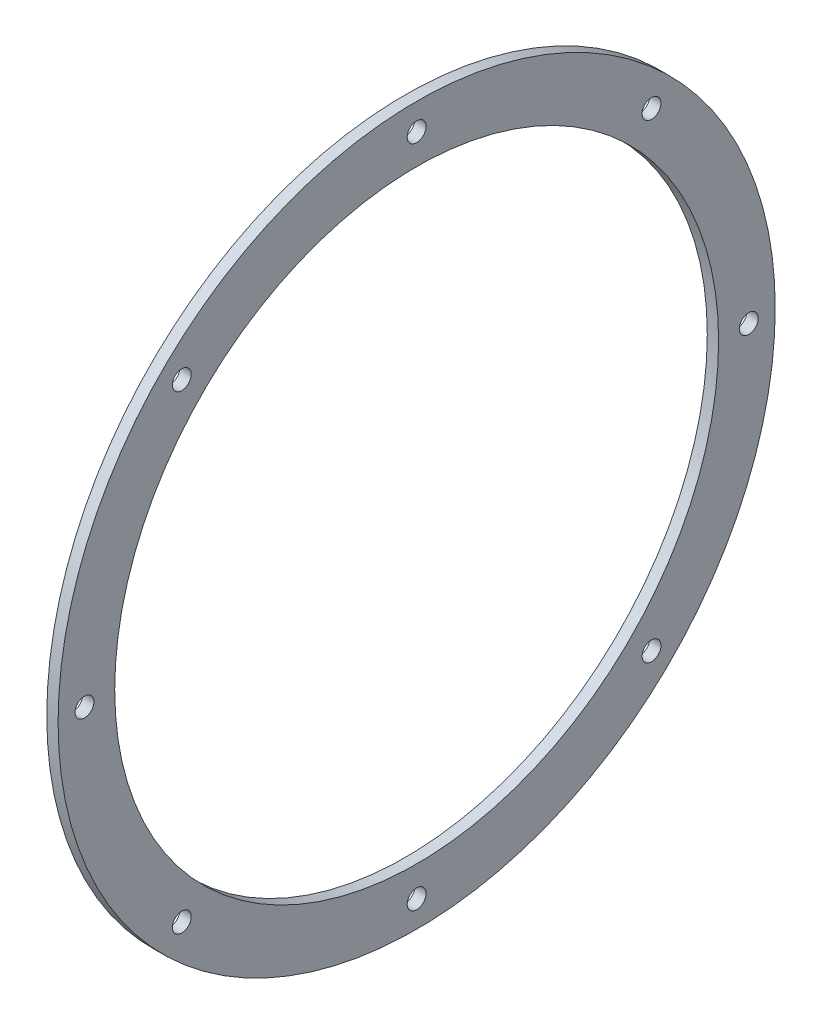
SolidWorks part; units mm, degrees
material "201 Stal nierdzewna odprężona (SS)"
ref_plane "Płaszczyzna przednia" through (0, 0, 0) normal (0, 0, 1) x (1, 0, 0)
ref_plane "Płaszczyzna górna" through (0, 0, 0) normal (0, 1, 0) x (1, 0, 0)
ref_plane "Płaszczyzna prawa" through (0, 0, 0) normal (1, 0, 0) x (0, 0, -1)
sketch "Szkic1" plane through (0, 0, 0) normal (1, 0, 0) x (0, 0, -1)
  circle A0 centre (0, 0) radius 80
  circle A1 centre (0, 0) radius 95
  circle A2 centre (0, 88) radius 2.5
  circle A3 centre (62.2254, 62.2254) radius 2.5
  circle A4 centre (88, 0) radius 2.5
  circle A5 centre (62.2254, -62.2254) radius 2.5
  circle A6 centre (0, -88) radius 2.5
  circle A7 centre (-62.2254, -62.2254) radius 2.5
  circle A8 centre (-88, 0) radius 2.5
  circle A9 centre (-62.2254, 62.2254) radius 2.5
  point P22 (0, 0)
  dimension "D1" = 160
  dimension "D2" = 190
  dimension "D3" = 5
  dimension "D4" = 88
  dimension "D5" = 8
extrude "Dodanie-wyciągnięcie1" add sketch "Szkic1" along normal blind 3
